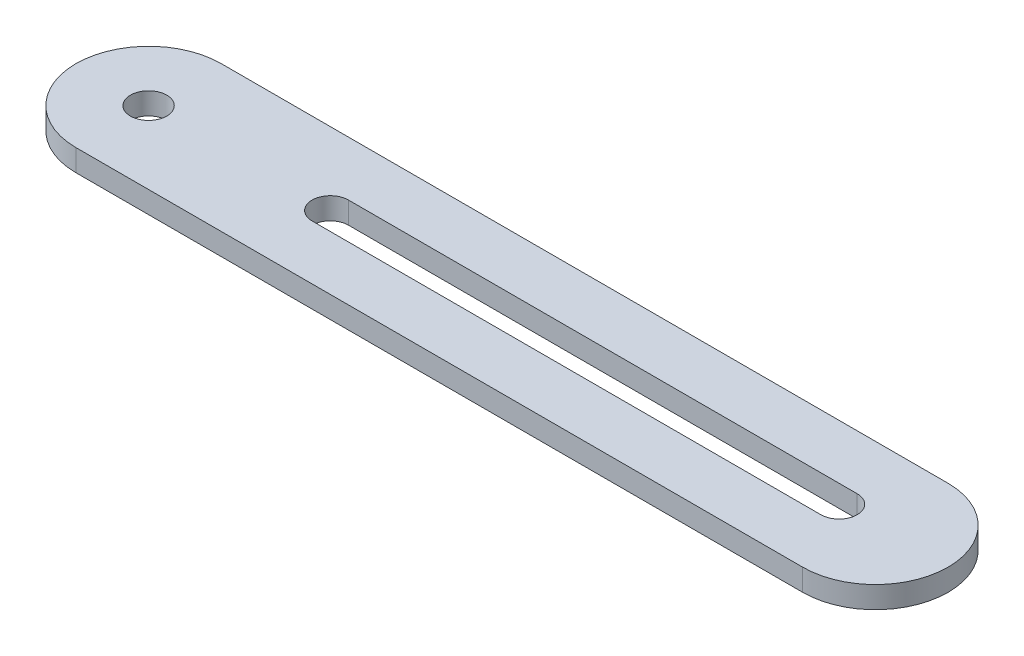
SolidWorks part; units mm, degrees
ref_plane "Front Plane" through (0, 0, 0) normal (0, 0, 1) x (1, 0, 0)
ref_plane "Top Plane" through (0, 0, 0) normal (0, 1, 0) x (1, 0, 0)
ref_plane "Right Plane" through (0, 0, 0) normal (1, 0, 0) x (0, 0, -1)
sketch "Sketch1" plane through (0, 0, 0) normal (0, 1, 0) x (1, 0, 0)
  line L0 (-50, 0) -> (50, 0) construction
  line L1 (-50, 10) -> (50, 10)
  line L2 (-50, -10) -> (50, -10)
  line L3 (-25, 0) -> (45, 0) construction
  line L6 (-25, 2.5) -> (45, 2.5)
  line L7 (-25, -2.5) -> (45, -2.5)
  arc A0 (-50, 10) -> (-50, -10) centre (-50, 0) ccw
  arc A1 (50, -10) -> (50, 10) centre (50, 0) ccw
  circle A4 centre (-50, 0) radius 2.5
  arc A5 (-25, 2.5) -> (-25, -2.5) centre (-25, 0) ccw
  arc A6 (45, -2.5) -> (45, 2.5) centre (45, 0) ccw
  point P2 (0, 0)
  point P10 (10, 0)
  dimension "D2" = 10
  dimension "D3" = 2.5
  dimension "D4" = 5
  dimension "D1" = 100
  dimension "D5" = 70
  dimension "D6" = 10
base flange "Base-Flange1" sketch "Sketch1" thickness 3 reverse thickness direction no parameters "D1"=3
sketch "Bend-Lines1" [suppressed] plane through (0, 0, 0) normal (0, 1, 0) x (1, 0, 0)
sketch "Bounding-Box1" [suppressed] plane through (0, 0, 0) normal (0, 1, 0) x (1, 0, 0)
sheet metal parameters "Sheet-Metal1" thickness 3 parameters "D1"=3
flat pattern "Flat-Pattern1" [suppressed]
sketch "Bend-Lines2" plane through (0, 0, 0) normal (0, 1, 0) x (1, 0, 0)
sketch3d "Bounding-Box2" [suppressed]
  line L0 (110, -10, 0) -> (-10, -10, 0) construction
  line L1 (110, 10, 0) -> (-10, 10, 0) construction
  line L2 (110, -10, 0) -> (110, 10, 0) construction
  line L3 (-10, -10, 0) -> (-10, 10, 0) construction
